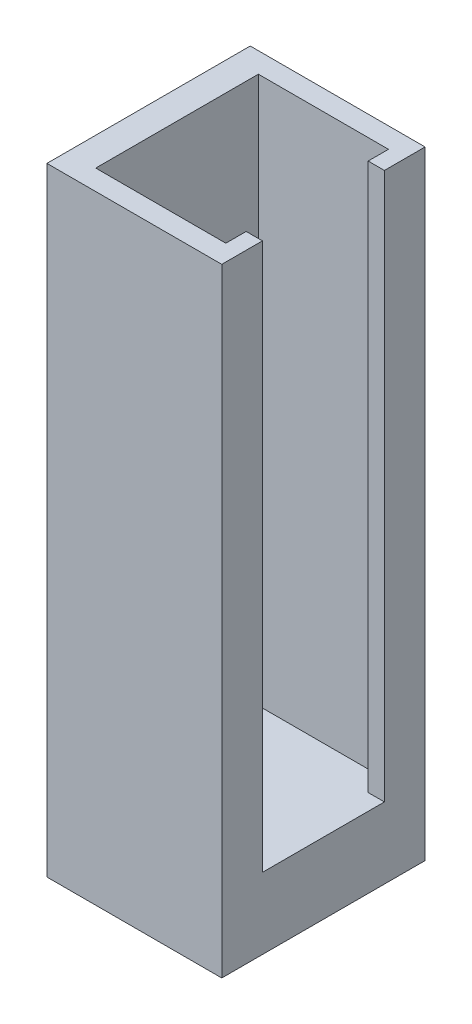
SolidWorks part; units mm, degrees
ref_plane "Front Plane" through (0, 0, 0) normal (0, 0, 1) x (1, 0, 0)
ref_plane "Top Plane" through (0, 0, 0) normal (0, 1, 0) x (1, 0, 0)
ref_plane "Right Plane" through (0, 0, 0) normal (1, 0, 0) x (0, 0, -1)
sketch "Sketch1" plane through (0, 0, 0) normal (0, 0, 1) x (1, 0, 0)
  line L1 (-2.15, 0) -> (2.15, 0)
  line L2 (-2.15, 0) -> (-2.15, 15.2)
  line L3 (-2.15, 15.2) -> (2.15, 15.2)
  line L4 (2.15, 0) -> (2.15, 15.2)
  point P5 (0, 0)
  dimension "D1" = 15.2
  dimension "D2" = 4.3
extrude "Boss-Extrude1" add sketch "Sketch1" along normal mid plane 5
sketch "Sketch3" plane through (0, 0, 0) normal (0, -1, 0) x (-1, 0, 0)
  line L0 (-2.15, -1.5) -> (-1.75, -1.5)
  line L1 (-2.15, -2.5) -> (-2.15, 2.5) construction
  line L2 (-1.75, -1.5) -> (-1.75, -2)
  line L3 (-1.75, -2) -> (1.45, -2)
  line L4 (1.45, -2) -> (1.45, 2)
  line L5 (1.45, 2) -> (-1.75, 2)
  line L6 (-1.75, 2) -> (-1.75, 1.5)
  line L7 (-1.75, 1.5) -> (-2.15, 1.5)
  line L8 (-2.15, 1.5) -> (-2.15, -1.5)
  line L9 (-2.15, 0) -> (1.45, 0) construction
  line L10 (2.15, -2.5) -> (-2.15, -2.5) construction
  line L11 (2.15, -2.5) -> (2.15, 2.5) construction
  dimension "D1" = 3
  dimension "D2" = 0.5
  dimension "D3" = 0.7
  dimension "D4" = 3.2
extrude "Cut-Extrude1" cut sketch "Sketch3" against normal through all from offset 1.75 offset against normal yes
